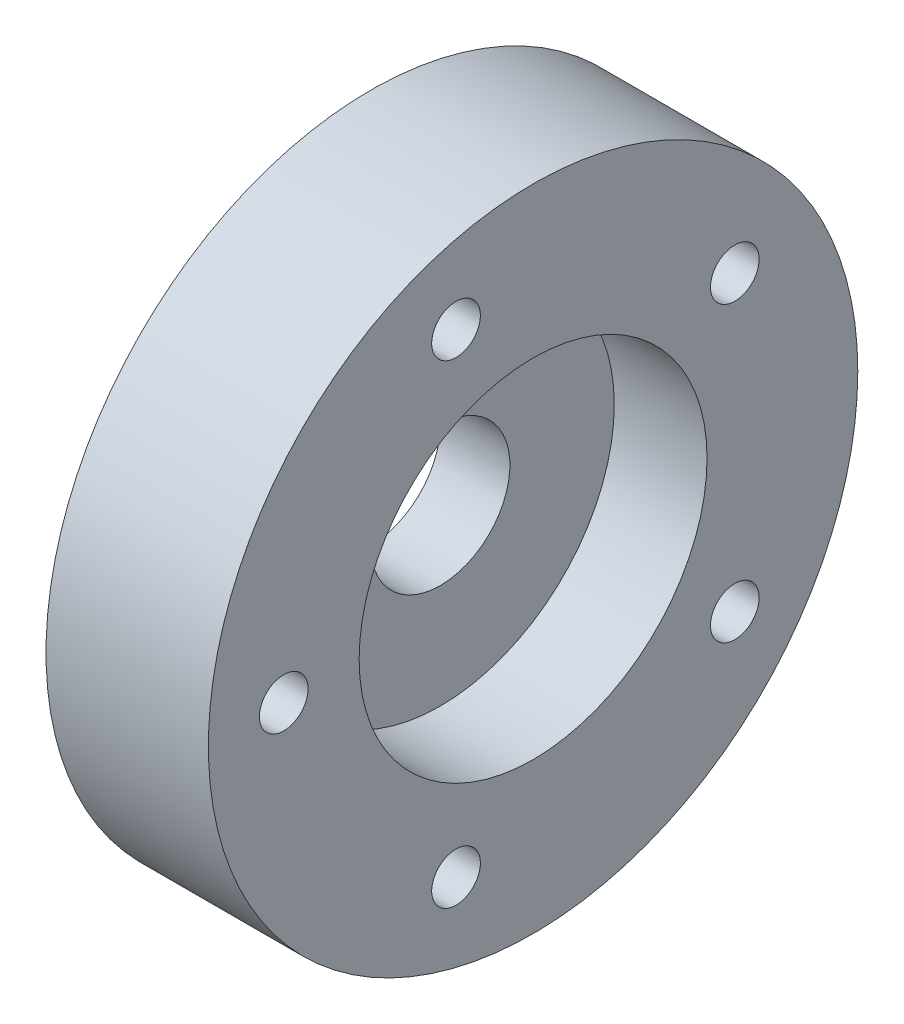
SolidWorks part; units mm, degrees
material "6061-T6 (SS)"
ref_plane "Front Plane" through (0, 0, 0) normal (1, 0, 0) x (0, 1, 0)
ref_plane "Top Plane" through (0, 0, 0) normal (0, 0, 1) x (0, 1, 0)
ref_plane "Right Plane" through (0, 0, 0) normal (0, 1, 0) x (-1, 0, 0)
sketch "Sketch1" plane through (0, 0, 0) normal (1, 0, 0) x (0, 1, 0)
  circle A0 centre (0, 0) radius 28
  dimension "D1" = 56
extrude "Boss-Extrude1" add sketch "Sketch1" along normal blind 14
sketch "Sketch2" plane through (14, 0, 0) normal (1, 0, 0) x (0, 1, 0)
  circle A0 centre (0, 0) radius 15
  dimension "D1" = 30
extrude "Cut-Extrude1" cut sketch "Sketch2" against normal blind 8
sketch "Sketch3" plane through (0, 0, 0) normal (-1, 0, 0) x (0, -1, 0)
  line L0 (0, 0) -> (0, 7.7969) construction
  line L1 (-2, 7.7969) -> (2, 7.7969)
  line L2 (-2, 7.7969) -> (-2, 5.6569)
  line L3 (2, 7.7969) -> (2, 5.6569)
  arc A0 (-2, 5.6569) -> (2, 5.6569) centre (0, 0) ccw
  point P7 (0, 7.7969)
  dimension "D1" = 12
  dimension "D2" = 4
  dimension "D3" = 2.14
extrude "Cut-Extrude2" cut sketch "Sketch3" against normal blind 16
sketch "Sketch9" plane through (14, 0, 0) normal (1, 0, 0) x (0, 1, 0)
  circle A1 centre (0, 0) radius 21.5 construction
  circle A2 centre (0, 21.5) radius 1.5
  circle A3 centre (20.4477, 6.6439) radius 1.5
  circle A4 centre (12.6374, -17.3939) radius 1.5
  circle A5 centre (-12.6374, -17.3939) radius 1.5
  circle A6 centre (-20.4477, 6.6439) radius 1.5
  point P15 (0, 0)
  dimension "D1" = 3
  dimension "D2" = 43
  dimension "D3" = 5
hole_wizard "M5x0.8 Tapped Hole1" positions "3DSketch5" profile "Sketch10" tap size "M5x0.8" standard "ANSI Metric"
sketch3d "3DSketch5"
  point P0 (14, -20.4477, 6.6439)
  point P3 (14, 0, 21.5)
  point P6 (14, -12.6374, -17.3939)
  point P9 (14, 12.6374, -17.3939)
  point P12 (14, 20.4477, 6.6439)
sketch "Sketch10" plane through (14, -20.4477, 6.6439) normal (0, 1, 0) x (0, 0, -1)
  line L0 (0, 0) -> (0, 9.2618)
  line L1 (0, 9.2618) -> (2.1, 8)
  line L2 (2.1, 8) -> (2.1, 0)
  line L5 (2.1, 0) -> (0, 0)
  line L10 (0, 9.2618) -> (-2.1, 8) construction
  line L11 (0, -6.35) -> (0, 107.95) construction
  dimension "Tap Drill Dia." = 4.2
  dimension "Tap Drill Depth" = 8
  dimension "Drill Angle" = 118
